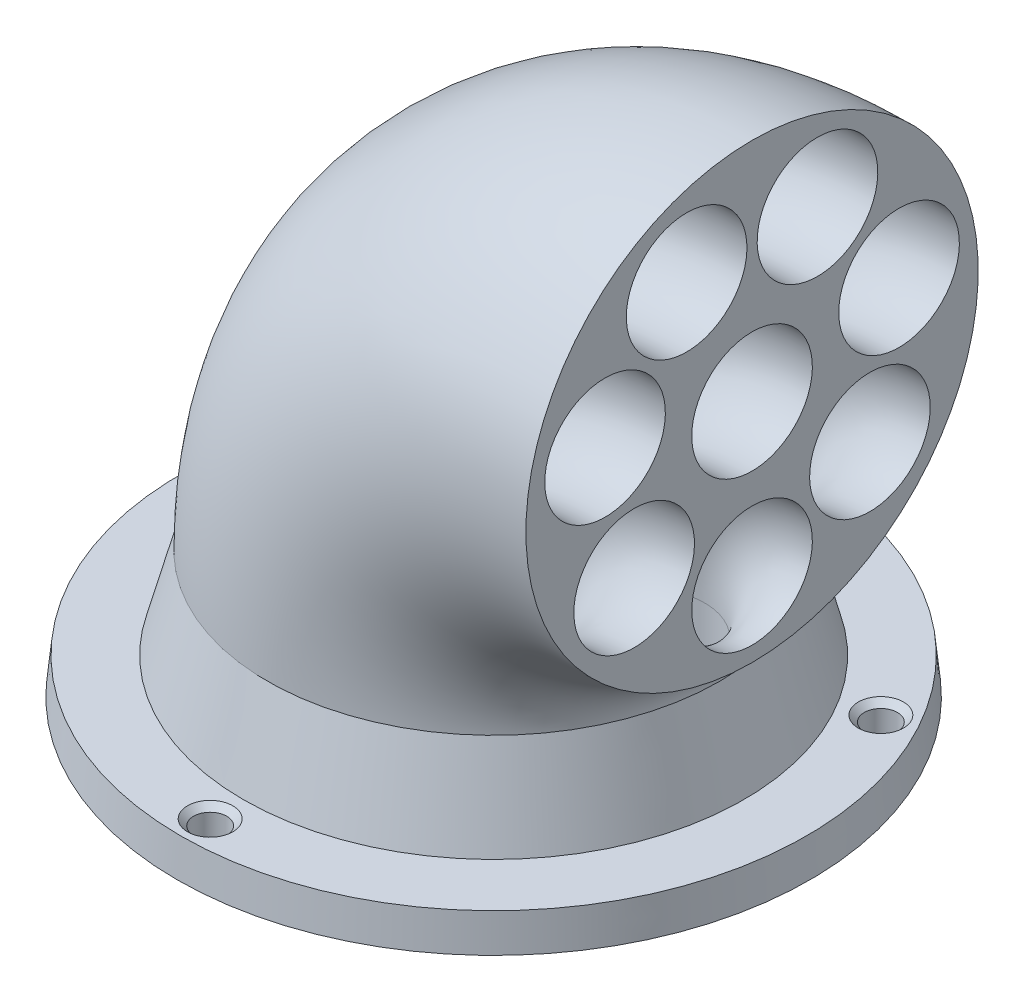
SolidWorks part; units mm, degrees
note: The reader was unsure of these and kept them because the rebuilt part matched: shared geometry of "Sketch1<6>", "Sketch1<8>".
other "Markup1"
sketch "Sketch2" plane through (25, 12.5, 25) normal (0.1814, 0.4325, 0.8832) x (0.9819, -0.0292, -0.1874)
ref_plane "Front Plane" through (0, 0, 0) normal (0, 0, 1) x (1, 0, 0)
ref_plane "Top Plane" through (0, 0, 0) normal (0, 1, 0) x (1, 0, 0)
ref_plane "Right Plane" through (0, 0, 0) normal (1, 0, 0) x (0, 0, -1)
sketch "Sketch1" plane through (0, 0, 0) normal (0, 1, 0) x (1, 0, 0)
  line L0 (0, 0) -> (12.5, 0)
  line L2 (12.5, 0) -> (7.7936, 9.7729)
  line L3 (7.7936, 9.7729) -> (-2.7815, 12.1866)
  line L4 (-2.7815, 12.1866) -> (-11.2621, 5.4235)
  line L5 (-11.2621, 5.4235) -> (-11.2621, -5.4235)
  line L6 (-11.2621, -5.4235) -> (-2.7815, -12.1866)
  line L7 (-2.7815, -12.1866) -> (7.7936, -9.7729)
  line L8 (7.7936, -9.7729) -> (12.5, 0)
  circle A0 centre (0, 0) radius 26.25
  circle A1 centre (0, 0) radius 5
  circle A2 centre (0, 0) radius 11.2621 construction
  arc A9 (0, -23.5) -> (20.3516, 11.75) centre (0, 0) cw
  circle A13 centre (0, 0) radius 18.75
  circle A17 centre (-2.7815, 12.1866) radius 5
  circle A18 centre (7.7936, 9.7729) radius 5
  circle A19 centre (12.5, 0) radius 5
  circle A20 centre (7.7936, -9.7729) radius 5
  circle A21 centre (-2.7815, -12.1866) radius 5
  circle A22 centre (-11.2621, -5.4235) radius 5
  circle A23 centre (-11.2621, 5.4235) radius 5
  circle A24 centre (0, -23.5) radius 1.375
  circle A25 centre (20.3516, 11.75) radius 1.375
  circle A26 centre (-20.3516, 11.75) radius 1.375
  dimension "D1" = 52.5
  dimension "D2" = 12.5
  dimension "D3" = 37.5
  dimension "D5" = 10
extrude "Boss-Extrude3" add sketch "Sketch1" along normal blind 3
extrude "Boss-Extrude4" add sketch "Sketch1<6>" along normal blind 7.5 from surface at 3
sketch "Sketch1<6>" plane through (0, 0, 0) normal (0, 1, 0) x (1, 0, 0) same geometry as "Sketch1"
fillet "Fillet3" radius 2 1 edges at (0, 3, 18.75) profile chamfer first distance on face at (0, 3, 26.25)
chamfer "Chamfer4" distance 0.5 angle 45 3 edges at (-20.3516, 3, -10.375) (20.3516, 3, -10.375) (0, 3, 24.875)
chamfer "Chamfer5" [suppressed] distance 0.5 angle 45
chamfer "Chamfer6" distance 3 distance2 0.3 1 edges at (0, 3, 26.25) first distance on face at (0, 3, 26.25)
extrude "Boss-Extrude6" add sketch "Sketch1<8>" against normal blind 4 contours L4 A23 L5 | L5 A23 L4 | L6 A22 L5 | L5 A22 L6
sketch "Sketch1<8>" plane through (0, 0, 0) normal (0, 1, 0) x (1, 0, 0) same geometry as "Sketch1"
sketch "Sketch3" plane through (0, -4, 0) normal (0, -1, 0) x (1, 0, 0)
  line L0 (0, 0) -> (12.5, 0)
  line L2 (12.5, 0) -> (7.7936, 9.7729)
  line L3 (7.7936, 9.7729) -> (-2.7815, 12.1866)
  line L4 (-2.7815, 12.1866) -> (-11.2621, 5.4235)
  line L5 (-11.2621, 5.4235) -> (-11.2621, -5.4235)
  line L6 (-11.2621, -5.4235) -> (-2.7815, -12.1866)
  line L7 (-2.7815, -12.1866) -> (7.7936, -9.7729)
  line L8 (7.7936, -9.7729) -> (12.5, 0)
  circle A0 centre (0, 0) radius 11.2621 construction
  circle A1 centre (-2.7815, 12.1866) radius 4.75
  circle A2 centre (7.7936, 9.7729) radius 4.75
  circle A3 centre (12.5, 0) radius 4.75
  circle A4 centre (7.7936, -9.7729) radius 4.75
  circle A5 centre (-2.7815, -12.1866) radius 4.75
  circle A6 centre (-11.2621, -5.4235) radius 4.75
  circle A7 centre (-11.2621, 5.4235) radius 4.75
  circle A8 centre (0, 0) radius 4.75
extrude "Boss-Extrude7" add sketch "Sketch3" along normal blind 2.5
chamfer "Chamfer7" distance 4.75 distance2 2.5 7 edges at (-11.2621, -4, 0) (-7.0218, -4, -8.8051) (2.5061, -4, -10.9797) (10.1468, -4, -4.8864) (10.1468, -4, 4.8864) (2.5061, -4, 10.9797) (-7.0218, -4, 8.8051) first distance on face at (0, -4, 18.75)
chamfer "Chamfer8" distance 4 distance2 2 1 edges at (0, 0, 18.75) first distance on face at (0, -4, 18.75)
sketch "Sketch4" plane through (0, 10.5, 0) normal (0, 1, 0) x (1, 0, 0)
  line L0 (18.75, 0) -> (21.4231, 0)
  line L1 (21.4231, -31.4432) -> (21.4231, 31.4432)
  circle A0 centre (0, 0) radius 18.75
  circle A1 centre (0, 0) radius 5
  circle A2 centre (12.5, 0) radius 5
  circle A3 centre (7.7936, 9.7729) radius 5
  circle A4 centre (-2.7815, 12.1866) radius 5
  circle A5 centre (-11.2621, 5.4235) radius 5
  circle A6 centre (-11.2621, -5.4235) radius 5
  circle A7 centre (-2.7815, -12.1866) radius 5
  circle A8 centre (7.7936, -9.7729) radius 5
  point P28 (18.75, 0)
  point P32 (21.4231, 0)
revolve "Revolve4" add sketch "Sketch4" angle 90 about L1
